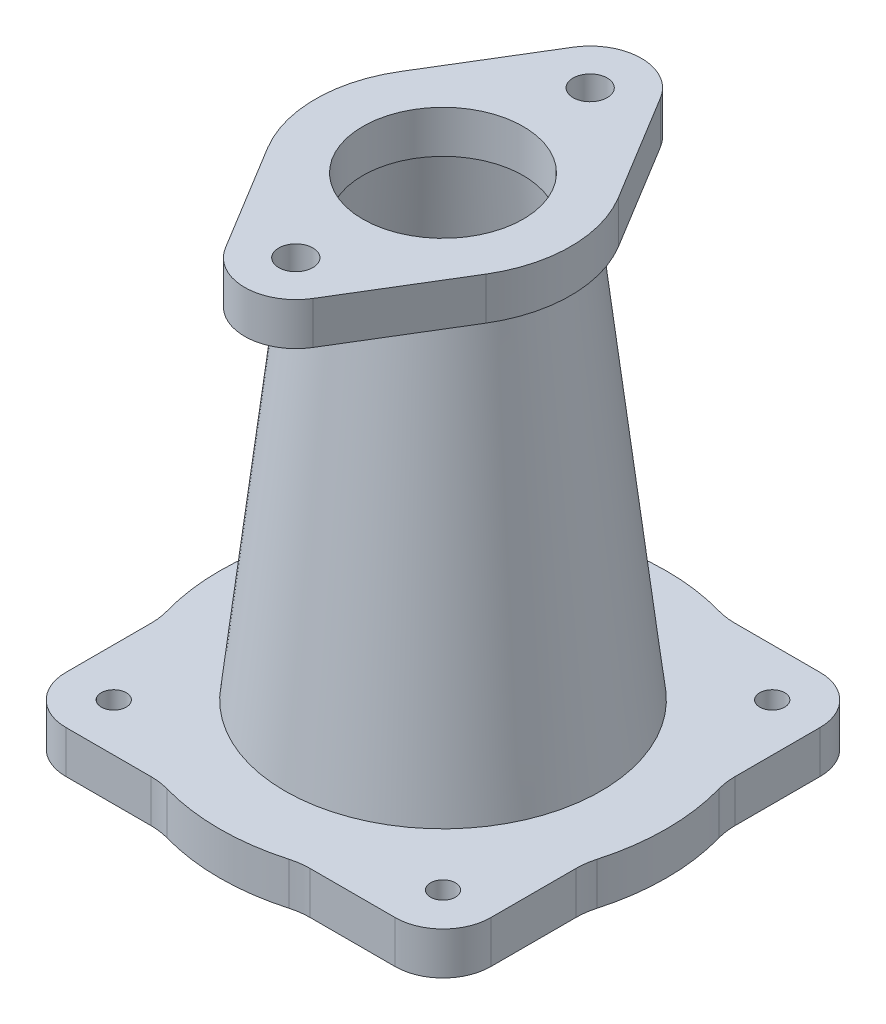
SolidWorks part; units mm, degrees
ref_plane "Front Plane" through (0, 0, 0) normal (0, 0, 1) x (1, 0, 0)
ref_plane "Top Plane" through (0, 0, 0) normal (0, 1, 0) x (1, 0, 0)
ref_plane "Right Plane" through (0, 0, 0) normal (1, 0, 0) x (0, 0, -1)
sketch "Sketch1" plane through (0, 0, 0) normal (1, 0, 0) x (0, 0, -1)
  line L0 (0, 0) -> (0, 51.6773) construction
  line L1 (12, 74.5842) -> (15.8346, 74.5842)
  line L2 (15.8346, 74.5842) -> (24.3324, 0)
  line L3 (24.3324, 0) -> (20.4978, 0)
  line L4 (20.4978, 0) -> (12, 74.5842)
  line L5 (6.7611, 0) -> (-6.7611, 0) construction
  dimension "D1" = 3.81
  dimension "D2" = 83.5
  dimension "D3" = 20.4978
  dimension "D4" = 12
revolve "Revolve1" add sketch "Sketch1" angle 360 about L0
sketch "Sketch2" plane through (0, 0, 0) normal (0, -1, 0) x (1, 0, 0)
  line L1 (0, 0) -> (0, 15.1186) construction
  line L2 (0, 0) -> (14.8797, 0) construction
  line L3 (-31.75, 11.8791) -> (-31.75, 24.6063)
  line L4 (-24.6062, -31.75) -> (-11.8791, -31.75)
  line L5 (-31.75, -24.6062) -> (-31.75, -11.8791)
  line L6 (-24.6062, 31.75) -> (-11.8791, 31.75)
  line L7 (31.75, -24.6062) -> (31.75, -11.8791)
  line L8 (11.8791, 31.75) -> (24.6063, 31.75)
  line L9 (31.75, 11.8791) -> (31.75, 24.6063)
  line L10 (11.8791, -31.75) -> (24.6063, -31.75)
  circle A4 centre (0, 0) radius 22.1742
  circle A5 centre (24.6063, 24.6063) radius 1.8669
  circle A6 centre (24.6063, -24.6062) radius 1.8669
  circle A7 centre (-24.6062, -24.6062) radius 1.8669
  circle A8 centre (-24.6062, 24.6063) radius 1.8669
  arc A9 (-24.6062, 31.75) -> (-31.75, 24.6063) centre (-24.6062, 24.6063) ccw
  arc A10 (24.6063, -31.75) -> (31.75, -24.6062) centre (24.6063, -24.6062) ccw
  arc A11 (-31.75, -24.6062) -> (-24.6062, -31.75) centre (-24.6062, -24.6062) ccw
  arc A12 (31.75, 24.6063) -> (24.6063, 31.75) centre (24.6063, 24.6063) ccw
  arc A13 (-32.1351, 9.1085) -> (-32.1351, -9.1085) centre (0, 0) ccw
  arc A14 (-9.1085, -32.1351) -> (9.1085, -32.1351) centre (0, 0) ccw
  arc A15 (9.1085, 32.1351) -> (-9.1085, 32.1351) centre (0, 0) ccw
  arc A16 (32.1351, -9.1085) -> (32.1351, 9.1085) centre (0, 0) ccw
  arc A17 (32.1351, 9.1085) -> (31.75, 11.8791) centre (41.91, 11.8791) cw
  arc A18 (31.75, -11.8791) -> (32.1351, -9.1085) centre (41.91, -11.8791) cw
  arc A19 (9.1085, -32.1351) -> (11.8791, -31.75) centre (11.8791, -41.91) cw
  arc A20 (-9.1085, -32.1351) -> (-11.8791, -31.75) centre (-11.8791, -41.91) ccw
  arc A21 (-31.75, -11.8791) -> (-32.1351, -9.1085) centre (-41.91, -11.8791) ccw
  arc A22 (-32.1351, 9.1085) -> (-31.75, 11.8791) centre (-41.91, 11.8791) ccw
  arc A23 (-9.1085, 32.1351) -> (-11.8791, 31.75) centre (-11.8791, 41.91) cw
  arc A24 (11.8791, 31.75) -> (9.1085, 32.1351) centre (11.8791, 41.91) cw
  dimension "D3" = 3.7338
  dimension "D4" = 44.3484
  dimension "D19" = 10.16
  dimension "D5" = 31.75
  dimension "D6" = 31.75
  dimension "D11" = 7.1437
  dimension "D12" = 7.1437
  dimension "D13" = 7.1437
  dimension "D14" = 7.1437
  dimension "D15" = 7.1437
  dimension "D16" = 7.1437
  dimension "D17" = 7.1437
  dimension "D18" = 7.1437
  dimension "D20" = 49.2125
extrude "Boss-Extrude1" add sketch "Sketch2" against normal blind 6.35
sketch "Sketch3" plane through (0, 74.5842, 0) normal (0, 1, 0) x (1, 0, 0)
  line L0 (0, 0) -> (21.5903, 0) construction
  line L2 (6.5434, -25.9787) -> (16.3097, -9.9171)
  line L3 (-16.3097, -9.9171) -> (-6.5434, -25.9787)
  line L4 (-16.3097, 9.9171) -> (-6.5434, 25.9787)
  line L5 (6.5434, 25.9787) -> (16.3097, 9.9171)
  circle A0 centre (0, 0) radius 12 construction
  circle A1 centre (0, 0) radius 12
  circle A2 centre (0, 22) radius 2.5527
  circle A3 centre (0, -22) radius 2.5527
  arc A4 (6.5434, 25.9787) -> (-6.5434, 25.9787) centre (0, 22) ccw
  arc A5 (-6.5434, -25.9787) -> (6.5434, -25.9787) centre (0, -22) ccw
  arc A6 (16.3097, -9.9171) -> (16.3097, 9.9171) centre (0, 0) ccw
  arc A7 (-16.3097, 9.9171) -> (-16.3097, -9.9171) centre (0, 0) ccw
  dimension "D1" = 44
  dimension "D2" = 5.1054
  dimension "D3" = 38.1762
  dimension "D4" = 15.3162
extrude "Boss-Extrude2" add sketch "Sketch3" against normal blind 6.35
